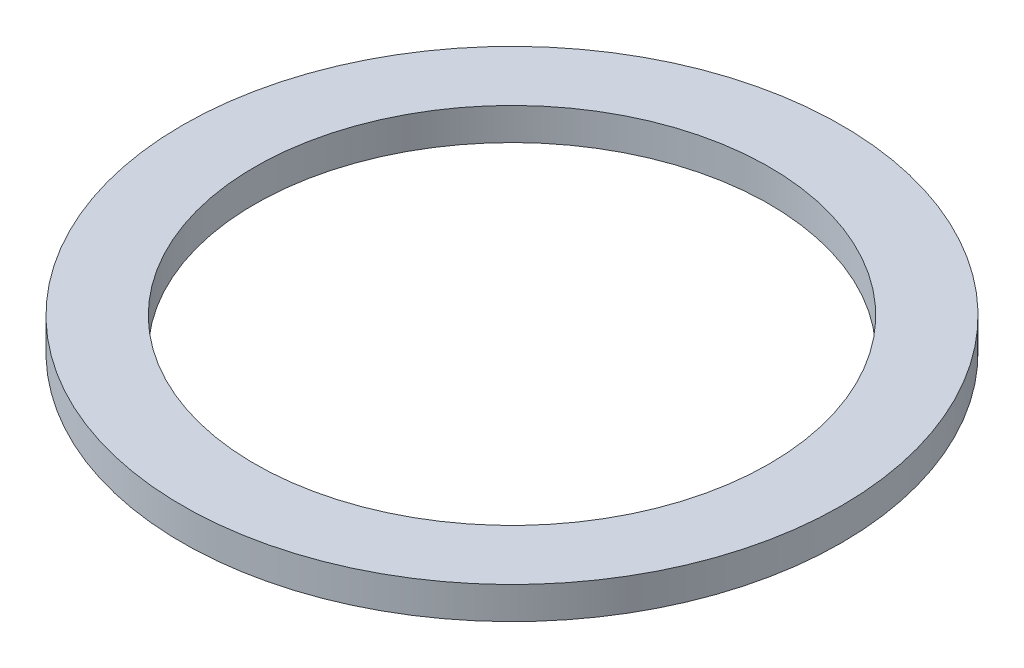
SolidWorks part; units mm, degrees
ref_plane "Front Plane" through (0, 0, 0) normal (0, 0, 1) x (1, 0, 0)
ref_plane "Top Plane" through (0, 0, 0) normal (0, 1, 0) x (1, 0, 0)
ref_plane "Right Plane" through (0, 0, 0) normal (1, 0, 0) x (0, 0, -1)
sketch "Sketch1" plane through (0, 0, 0) normal (0, 0, 1) x (1, 0, 0)
  line L0 (0, -200000) -> (0, 218797.9879) construction
  line L1 (130.175, 154.6921) -> (130.175, 141.9921) construction
  line L2 (101.6, 154.6921) -> (130.175, 154.6921) construction
  line L3 (122.68, 141.9921) -> (101.6, 141.9921) construction
  line L4 (101.6, 141.9921) -> (101.6, 154.6921) construction
  line L5 (0, -200000) -> (0, 218797.9879) construction
  line L6 (130.175, 154.6921) -> (130.175, 141.9921)
  line L7 (101.6, 154.6921) -> (130.175, 154.6921)
  line L8 (130.175, 141.9921) -> (101.6, 141.9921)
  line L9 (101.6, 141.9921) -> (101.6, 154.6921)
revolve "Revolve1" add sketch "Sketch1" angle 360 about L5
